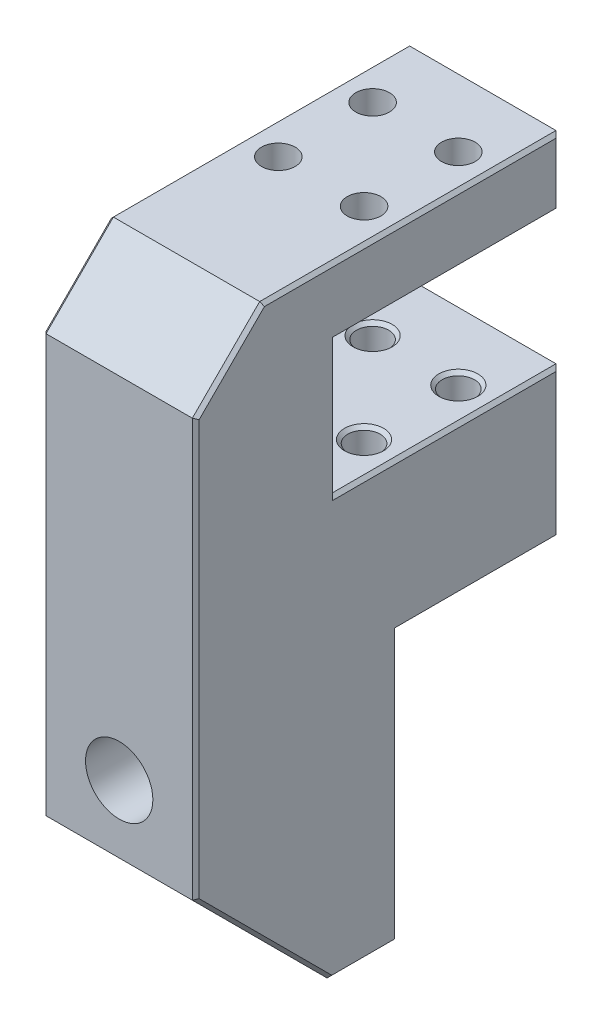
SolidWorks part; units mm, degrees
ref_plane "Front Plane" through (0, 0, 0) normal (0, 0, 1) x (1, 0, 0)
ref_plane "Top Plane" through (0, 0, 0) normal (0, 1, 0) x (1, 0, 0)
ref_plane "Right Plane" through (0, 0, 0) normal (1, 0, 0) x (0, 0, -1)
sketch "Sketch1" plane through (0, 0, 0) normal (0, 1, 0) x (1, 0, 0)
  line L1 (0, 0) -> (-12.73, 0)
  line L2 (0, 0) -> (0, 14)
  line L3 (0, 14) -> (-12.73, 14)
  line L4 (-12.73, 0) -> (-12.73, 14)
  line L5 (5, 24) -> (-17.73, 24)
  line L6 (5, 24) -> (5, -10)
  line L7 (5, -10) -> (-17.73, -10)
  line L8 (-17.73, 24) -> (-17.73, -10)
  circle A0 centre (-12.73, 14) radius 2.5
  circle A1 centre (0, 0) radius 2.5
  point P11 (0, 0)
  point P12 (0, 0)
  point P13 (0, 0)
  point P14 (0, 0)
  point P15 (0, 0)
  dimension "D3" = 5
  dimension "D1" = 14
  dimension "D2" = 12.73
  dimension "D4" = 5
  dimension "D5" = 5
  dimension "D6" = 10
  dimension "D7" = 10
sketch "Sketch2" plane through (0, 0, 0) normal (0, 1, 0) x (1, 0, 0)
  line L0 (5, 24) -> (-17.73, 24) construction
  line L1 (-17.73, 24) -> (-17.73, -10) construction
  line L2 (5, 24) -> (5, -10) construction
  line L3 (5, -10) -> (-17.73, -10) construction
  line L4 (5, 24) -> (-17.73, 24)
  line L5 (-17.73, 24) -> (-17.73, -10)
  line L6 (5, 24) -> (5, -10)
  line L7 (5, -10) -> (-17.73, -10)
extrude "Boss-Extrude1" add sketch "Sketch2" along normal blind 52
sketch "Sketch3" plane through (0, 0, 0) normal (0, -1, 0) x (1, 0, 0)
  line L0 (-17.73, -24) -> (-17.73, 10) construction
  line L1 (5, 10) -> (-17.73, 10)
  line L2 (5, 10) -> (5, 0)
  line L3 (5, 0) -> (-17.73, 0)
  line L4 (-17.73, 10) -> (-17.73, 0)
  dimension "D1" = 10
extrude "Boss-Extrude2" add sketch "Sketch3" along normal blind 40
sketch "Sketch4" plane through (0, 0, 10) normal (0, 0, 1) x (1, 0, 0)
  line L0 (-6.365, 0) -> (-6.365, -40) construction
  line L1 (5, -40) -> (-17.73, -40) construction
  line L2 (0, 0) -> (-6.365, 0) construction
  point P4 (-6.365, -30)
  point P6 (-6.365, -10)
  dimension "D1" = 10
  dimension "D2" = 10
hole_wizard "CBORE for M5 SHCS1" positions "Sketch5" profile "Sketch6" counterbore size "M5" standard "ANSI Metric" end condition through all
sketch "Sketch5" plane through (0, 0, 10) normal (0, 0, 1) x (1, 0, 0)
  point P0 (-6.365, -10)
  point P3 (-6.365, -30)
sketch "Sketch6" plane through (-6.365, -10, 10) normal (1, 0, 0) x (0, -1, 0)
  line L0 (0, 0) -> (0, 34)
  line L1 (0, 34) -> (2.75, 34)
  line L3 (2.75, 34) -> (2.75, 5)
  line L4 (2.75, 5) -> (5, 5)
  line L5 (5, 5) -> (5, 0)
  line L7 (5, 0) -> (0, 0)
  line L11 (0, -6.35) -> (0, 107.95) construction
  dimension "Thru Hole Dia." = 5.5
  dimension "Thru Hole Depth" = 34
  dimension "C'Bore Dia." = 10
  dimension "C'Bore Depth" = 5
sketch "Sketch7" plane through (0, 0, 10) normal (0, 0, 1) x (1, 0, 0)
  line L4 (-17.73, 52) -> (-17.73, -40)
  line L5 (-17.73, -40) -> (5, -40)
  line L6 (5, -40) -> (5, 52)
  line L7 (5, 52) -> (-17.73, 52)
  line L8 (-17.73, 52) -> (-17.73, -40)
  line L9 (-17.73, -40) -> (5, -40)
  line L10 (5, -40) -> (5, 52)
  line L11 (5, 52) -> (-17.73, 52)
  circle A0 centre (-6.365, -30) radius 5 construction
  circle A1 centre (-6.365, -10) radius 5 construction
  circle A2 centre (-6.365, -30) radius 5
  circle A3 centre (-6.365, -10) radius 5
  dimension "D1" = 0
extrude "Boss-Extrude3" add sketch "Sketch7" along normal blind 20
sketch "Sketch8" plane through (5, 0, 0) normal (1, 0, 0) x (0, 0, -1)
  line L0 (24, 52) -> (24, 0) construction
  line L1 (24, 42) -> (-9.2, 42)
  line L2 (24, 42) -> (24, 22)
  line L3 (24, 22) -> (-9.2, 22)
  line L4 (-9.2, 42) -> (-9.2, 22)
  line L5 (-30, 52) -> (24, 52) construction
  dimension "D1" = 20
  dimension "D2" = 10
  dimension "D3" = 9.2
extrude "Cut-Extrude1" cut sketch "Sketch8" against normal through all
sketch "Sketch9" plane through (0, 52, 0) normal (0, 1, 0) x (1, 0, 0)
  circle A1 centre (-12.73, 0) radius 2.5
  circle A2 centre (0, 14) radius 2.5
  circle A3 centre (-12.73, 14) radius 2.5
  circle A4 centre (0, 0) radius 2.5
  point P8 (0, 0)
  point P10 (-11.4975, -5.6474)
  point P12 (0, 0)
  point P13 (-10.9696, 16.0597)
  point P15 (0, 14.5136)
  point P17 (0, 0)
  dimension "D1" = 5
extrude "Cut-Extrude2" cut sketch "Sketch9" against normal up to next
sketch "Sketch10" plane through (0, 22, 0) normal (0, 1, 0) x (1, 0, 0)
  circle A0 centre (0, 0) radius 2.4
  circle A1 centre (-12.73, 0) radius 2.4
  circle A2 centre (-12.73, 14) radius 2.4
  circle A3 centre (0, 14) radius 2.4
  dimension "D1" = 4.8
extrude "Cut-Extrude3" cut sketch "Sketch10" against normal blind 20
chamfer "Chamfer1" distance 20 angle 45 1 edges at (-6.365, -40, 30)
chamfer "Chamfer3" distance 10 angle 45 1 edges at (-6.365, 52, 30)
chamfer "Chamfer2" distance 0.5 angle 45 28 edges at (5, 52, -2) (5, 11, -24) (5, 47, -24) (5, 0, -12) (5, -20, 0) (5, -40, 5) (5, -30, 20) (5, 11, 30) (-17.73, -20, 0) (-17.73, 0, -12) (-17.73, 47, -24) (-17.73, 11, -24) (-17.73, 52, -2) (-17.73, 11, 30) (-17.73, -30, 20) (-17.73, -40, 5) (5, 42, -7.4) (5, 32, 9.2) (5, 22, -7.4) (-17.73, 22, -7.4) (-17.73, 32, 9.2) (-17.73, 42, -7.4) (0, 22, -11.6) (-12.73, 22, -11.6) (-12.73, 22, 2.4) (0, 22, 2.4) (5, 47, 25) (-17.73, 47, 25)
